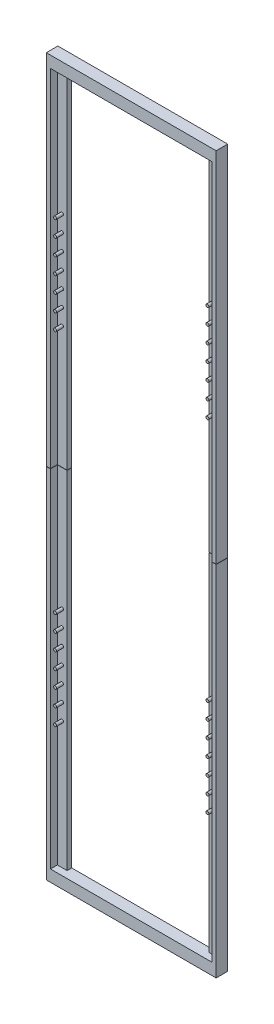
SolidWorks part; units mm, degrees
ref_plane "Front Plane" through (0, 0, 0) normal (1, 0, 0) x (0, 1, 0)
ref_plane "Top Plane" through (0, 0, 0) normal (0, 0, 1) x (0, 1, 0)
ref_plane "Right Plane" through (0, 0, 0) normal (0, 1, 0) x (-1, 0, 0)
sketch "Sketch1" plane through (0, 0, 0) normal (0, 0, 1) x (0, 1, 0)
  line L1 (-150, -30.75) -> (150, -30.75)
  line L2 (-150, -30.75) -> (-150, 30.75)
  line L3 (-150, 30.75) -> (150, 30.75)
  line L4 (150, -30.75) -> (150, 30.75)
  line L5 (-150, -30.75) -> (150, 30.75) construction
  line L6 (-150, 30.75) -> (150, -30.75) construction
  line L7 (-155, -36.75) -> (155, -36.75)
  line L8 (-155, -36.75) -> (-155, 36.75)
  line L9 (-155, 36.75) -> (155, 36.75)
  line L10 (155, -36.75) -> (155, 36.75)
  line L11 (-155, -36.75) -> (155, 36.75) construction
  line L12 (-155, 36.75) -> (155, -36.75) construction
  point P0 (0, 0)
  point P6 (0, 0)
  dimension "D1" = 61.5
  dimension "D2" = 6
  dimension "D3" = 300
  dimension "D4" = 310
extrude "Boss-Extrude1" add sketch "Sketch1" along normal blind 5
sketch "Sketch2" plane through (0, 0, 5) normal (0, 0, 1) x (1, 0, 0)
  line L1 (-30.75, 150) -> (-34.95, 150)
  line L2 (-30.75, 150) -> (-30.75, -150)
  line L3 (-30.75, -150) -> (-34.95, -150)
  line L4 (-34.95, 150) -> (-34.95, -150)
  line L5 (30.75, -150) -> (34.95, -150)
  line L6 (30.75, -150) -> (30.75, 150)
  line L7 (30.75, 150) -> (34.95, 150)
  line L8 (34.95, -150) -> (34.95, 150)
  dimension "D1" = 4.2
  dimension "D2" = 4.2
ref_plane "Plane1" through (-36.75, 155, 5) normal (0, -1, 0) x (-1, 0, 0)
extrude "Cut-Extrude1" cut sketch "Sketch2" against normal blind 3 contours L4 L3 L2 L1 | L8 L7 L6 L5
sketch "Sketch6" plane through (0, 0, 2) normal (0, 0, 1) x (1, 0, 0)
  line L4 (30.75, -150) -> (34.95, -150)
  line L5 (34.95, -150) -> (34.95, 150)
  line L6 (34.95, 150) -> (30.75, 150)
  line L7 (30.75, 150) -> (30.75, -150)
  line L8 (30.75, -150) -> (34.95, -150)
  line L9 (34.95, -150) -> (34.95, 150)
  line L10 (34.95, 150) -> (30.75, 150)
  line L11 (30.75, 150) -> (30.75, -150)
  dimension "D1" = 0
sketch "Sketch7" plane through (0, 0, 2) normal (0, 0, 1) x (1, 0, 0)
  line L0 (-31.65, 55) -> (-33.25, 55) construction
  line L1 (-34.45, 53.8) -> (-34.45, 52.2) construction
  line L2 (-33.25, 51) -> (-31.65, 51) construction
  line L3 (-30.45, 49.8) -> (-30.45, 56.2) construction
  line L4 (34.45, 66.2) -> (34.45, 67.8)
  line L5 (33.25, 69) -> (31.65, 69)
  line L6 (30.45, 70.2) -> (30.45, 63.8)
  line L7 (31.65, 65) -> (33.25, 65)
  line L8 (34.45, 66.2) -> (34.45, 67.8)
  line L9 (33.25, 69) -> (31.65, 69)
  line L10 (30.45, 70.2) -> (30.45, 63.8)
  line L11 (31.65, 65) -> (33.25, 65)
  line L12 (-31.65, 69) -> (-33.25, 69) construction
  line L13 (-34.45, 67.8) -> (-34.45, 66.2) construction
  line L14 (-33.25, 65) -> (-31.65, 65) construction
  line L15 (-30.45, 63.8) -> (-30.45, 70.2) construction
  line L16 (-31.65, -51) -> (-33.25, -51) construction
  line L17 (-34.45, -52.2) -> (-34.45, -53.8) construction
  line L18 (-33.25, -55) -> (-31.65, -55) construction
  line L19 (-30.45, -56.2) -> (-30.45, -49.8) construction
  line L20 (-31.65, -65) -> (-33.25, -65) construction
  line L21 (-34.45, -66.2) -> (-34.45, -67.8) construction
  line L22 (-33.25, -69) -> (-31.65, -69) construction
  line L23 (-30.45, -70.2) -> (-30.45, -63.8) construction
  line L24 (31.65, -69) -> (33.25, -69) construction
  line L25 (34.45, -67.8) -> (34.45, -66.2) construction
  line L26 (33.25, -65) -> (31.65, -65) construction
  line L27 (30.45, -63.8) -> (30.45, -70.2) construction
  line L28 (34.45, -53.8) -> (34.45, -52.2) construction
  line L29 (33.25, -51) -> (31.65, -51) construction
  line L30 (30.45, -49.8) -> (30.45, -56.2) construction
  line L31 (31.65, -55) -> (33.25, -55) construction
  line L32 (31.65, 51) -> (33.25, 51) construction
  line L33 (34.45, 52.2) -> (34.45, 53.8) construction
  line L34 (33.25, 55) -> (31.65, 55) construction
  line L35 (30.45, 56.2) -> (30.45, 49.8) construction
  line L36 (-31.65, 55) -> (-33.25, 55)
  line L37 (-34.45, 53.8) -> (-34.45, 52.2)
  line L38 (-33.25, 51) -> (-31.65, 51)
  line L39 (-30.45, 49.8) -> (-30.45, 56.2)
  line L40 (-31.65, 69) -> (-33.25, 69)
  line L41 (-34.45, 67.8) -> (-34.45, 66.2)
  line L42 (-33.25, 65) -> (-31.65, 65)
  line L43 (-30.45, 63.8) -> (-30.45, 70.2)
  line L44 (-31.65, -51) -> (-33.25, -51)
  line L45 (-34.45, -52.2) -> (-34.45, -53.8)
  line L46 (-33.25, -55) -> (-31.65, -55)
  line L47 (-30.45, -56.2) -> (-30.45, -49.8)
  line L48 (-31.65, -65) -> (-33.25, -65)
  line L49 (-34.45, -66.2) -> (-34.45, -67.8)
  line L50 (-33.25, -69) -> (-31.65, -69)
  line L51 (-30.45, -70.2) -> (-30.45, -63.8)
  line L52 (31.65, -69) -> (33.25, -69)
  line L53 (34.45, -67.8) -> (34.45, -66.2)
  line L54 (33.25, -65) -> (31.65, -65)
  line L55 (30.45, -63.8) -> (30.45, -70.2)
  line L56 (34.45, -53.8) -> (34.45, -52.2)
  line L57 (33.25, -51) -> (31.65, -51)
  line L58 (30.45, -49.8) -> (30.45, -56.2)
  line L59 (31.65, -55) -> (33.25, -55)
  line L60 (31.65, 51) -> (33.25, 51)
  line L61 (34.45, 52.2) -> (34.45, 53.8)
  line L62 (33.25, 55) -> (31.65, 55)
  line L63 (30.45, 56.2) -> (30.45, 49.8)
  arc A0 (-33.25, 55) -> (-34.45, 53.8) centre (-33.25, 53.8) ccw construction
  circle A1 centre (32.95, 67) radius 0.75
  circle A2 centre (32.95, 67) radius 0.75
  arc A3 (-34.45, 52.2) -> (-33.25, 51) centre (-33.25, 52.2) ccw construction
  arc A4 (-30.45, 49.8) -> (-31.65, 51) centre (-31.65, 49.8) ccw construction
  arc A5 (-31.65, 55) -> (-30.45, 56.2) centre (-31.65, 56.2) ccw construction
  arc A6 (34.45, 67.8) -> (33.25, 69) centre (33.25, 67.8) ccw
  arc A7 (30.45, 70.2) -> (31.65, 69) centre (31.65, 70.2) ccw
  arc A8 (31.65, 65) -> (30.45, 63.8) centre (31.65, 63.8) ccw
  arc A9 (33.25, 65) -> (34.45, 66.2) centre (33.25, 66.2) ccw
  arc A10 (34.45, 67.8) -> (33.25, 69) centre (33.25, 67.8) ccw
  arc A11 (30.45, 70.2) -> (31.65, 69) centre (31.65, 70.2) ccw
  arc A12 (31.65, 65) -> (30.45, 63.8) centre (31.65, 63.8) ccw
  arc A13 (33.25, 65) -> (34.45, 66.2) centre (33.25, 66.2) ccw
  arc A14 (-33.25, 69) -> (-34.45, 67.8) centre (-33.25, 67.8) ccw construction
  arc A15 (-34.45, 66.2) -> (-33.25, 65) centre (-33.25, 66.2) ccw construction
  arc A16 (-30.45, 63.8) -> (-31.65, 65) centre (-31.65, 63.8) ccw construction
  arc A17 (-31.65, 69) -> (-30.45, 70.2) centre (-31.65, 70.2) ccw construction
  arc A18 (-33.25, -51) -> (-34.45, -52.2) centre (-33.25, -52.2) ccw construction
  arc A19 (-34.45, -53.8) -> (-33.25, -55) centre (-33.25, -53.8) ccw construction
  arc A20 (-30.45, -56.2) -> (-31.65, -55) centre (-31.65, -56.2) ccw construction
  arc A21 (-31.65, -51) -> (-30.45, -49.8) centre (-31.65, -49.8) ccw construction
  arc A22 (-33.25, -65) -> (-34.45, -66.2) centre (-33.25, -66.2) ccw construction
  arc A23 (-34.45, -67.8) -> (-33.25, -69) centre (-33.25, -67.8) ccw construction
  arc A24 (-30.45, -70.2) -> (-31.65, -69) centre (-31.65, -70.2) ccw construction
  arc A25 (-31.65, -65) -> (-30.45, -63.8) centre (-31.65, -63.8) ccw construction
  arc A26 (33.25, -69) -> (34.45, -67.8) centre (33.25, -67.8) ccw construction
  arc A27 (34.45, -66.2) -> (33.25, -65) centre (33.25, -66.2) ccw construction
  arc A28 (30.45, -63.8) -> (31.65, -65) centre (31.65, -63.8) ccw construction
  arc A29 (31.65, -69) -> (30.45, -70.2) centre (31.65, -70.2) ccw construction
  arc A30 (34.45, -52.2) -> (33.25, -51) centre (33.25, -52.2) ccw construction
  arc A31 (30.45, -49.8) -> (31.65, -51) centre (31.65, -49.8) ccw construction
  arc A32 (31.65, -55) -> (30.45, -56.2) centre (31.65, -56.2) ccw construction
  arc A33 (33.25, -55) -> (34.45, -53.8) centre (33.25, -53.8) ccw construction
  arc A34 (33.25, 51) -> (34.45, 52.2) centre (33.25, 52.2) ccw construction
  arc A35 (34.45, 53.8) -> (33.25, 55) centre (33.25, 53.8) ccw construction
  arc A36 (30.45, 56.2) -> (31.65, 55) centre (31.65, 56.2) ccw construction
  arc A37 (31.65, 51) -> (30.45, 49.8) centre (31.65, 49.8) ccw construction
  arc A38 (-33.25, 55) -> (-34.45, 53.8) centre (-33.25, 53.8) ccw
  arc A39 (-34.45, 52.2) -> (-33.25, 51) centre (-33.25, 52.2) ccw
  arc A40 (-30.45, 49.8) -> (-31.65, 51) centre (-31.65, 49.8) ccw
  arc A41 (-31.65, 55) -> (-30.45, 56.2) centre (-31.65, 56.2) ccw
  arc A42 (-33.25, 69) -> (-34.45, 67.8) centre (-33.25, 67.8) ccw
  arc A43 (-34.45, 66.2) -> (-33.25, 65) centre (-33.25, 66.2) ccw
  arc A44 (-30.45, 63.8) -> (-31.65, 65) centre (-31.65, 63.8) ccw
  arc A45 (-31.65, 69) -> (-30.45, 70.2) centre (-31.65, 70.2) ccw
  arc A46 (-33.25, -51) -> (-34.45, -52.2) centre (-33.25, -52.2) ccw
  arc A47 (-34.45, -53.8) -> (-33.25, -55) centre (-33.25, -53.8) ccw
  arc A48 (-30.45, -56.2) -> (-31.65, -55) centre (-31.65, -56.2) ccw
  arc A49 (-31.65, -51) -> (-30.45, -49.8) centre (-31.65, -49.8) ccw
  arc A50 (-33.25, -65) -> (-34.45, -66.2) centre (-33.25, -66.2) ccw
  arc A51 (-34.45, -67.8) -> (-33.25, -69) centre (-33.25, -67.8) ccw
  arc A52 (-30.45, -70.2) -> (-31.65, -69) centre (-31.65, -70.2) ccw
  arc A53 (-31.65, -65) -> (-30.45, -63.8) centre (-31.65, -63.8) ccw
  arc A54 (33.25, -69) -> (34.45, -67.8) centre (33.25, -67.8) ccw
  arc A55 (34.45, -66.2) -> (33.25, -65) centre (33.25, -66.2) ccw
  arc A56 (30.45, -63.8) -> (31.65, -65) centre (31.65, -63.8) ccw
  arc A57 (31.65, -69) -> (30.45, -70.2) centre (31.65, -70.2) ccw
  arc A58 (34.45, -52.2) -> (33.25, -51) centre (33.25, -52.2) ccw
  arc A59 (30.45, -49.8) -> (31.65, -51) centre (31.65, -49.8) ccw
  arc A60 (31.65, -55) -> (30.45, -56.2) centre (31.65, -56.2) ccw
  arc A61 (33.25, -55) -> (34.45, -53.8) centre (33.25, -53.8) ccw
  arc A62 (33.25, 51) -> (34.45, 52.2) centre (33.25, 52.2) ccw
  arc A63 (34.45, 53.8) -> (33.25, 55) centre (33.25, 53.8) ccw
  arc A64 (30.45, 56.2) -> (31.65, 55) centre (31.65, 56.2) ccw
  arc A65 (31.65, 51) -> (30.45, 49.8) centre (31.65, 49.8) ccw
  circle A66 centre (32.95, 53) radius 0.75 construction
  circle A67 centre (32.95, -53) radius 0.75 construction
  circle A68 centre (32.95, -67) radius 0.75 construction
  circle A69 centre (-32.95, -67) radius 0.75 construction
  circle A70 centre (-32.95, -53) radius 0.75 construction
  circle A71 centre (-32.95, 53) radius 0.75 construction
  circle A72 centre (-32.95, 67) radius 0.75 construction
  circle A73 centre (32.95, 53) radius 0.75
  circle A74 centre (32.95, -53) radius 0.75
  circle A75 centre (32.95, -67) radius 0.75
  circle A76 centre (-32.95, -67) radius 0.75
  circle A77 centre (-32.95, -53) radius 0.75
  circle A78 centre (-32.95, 53) radius 0.75
  circle A79 centre (-32.95, 67) radius 0.75
  circle A80 centre (-32.95, -67) radius 0.65
  circle A81 centre (-32.95, -53) radius 0.65
  circle A82 centre (-32.95, 53) radius 0.65
  circle A83 centre (-32.95, 67) radius 0.65
  circle A84 centre (32.95, 67) radius 0.65
  circle A85 centre (32.95, 53) radius 0.65
  circle A86 centre (32.95, -53) radius 0.65
  circle A87 centre (32.95, -67) radius 0.65
  circle A88 centre (32.95, -60) radius 0.65
  circle A89 centre (32.95, -74) radius 0.65
  circle A90 centre (32.95, -67) radius 0.65
  circle A91 centre (32.95, -81) radius 0.65
  circle A92 centre (32.95, -74) radius 0.65
  circle A93 centre (32.95, -88) radius 0.65
  circle A94 centre (32.95, -81) radius 0.65
  circle A95 centre (32.95, -95) radius 0.65
  circle A96 centre (-32.95, -74) radius 0.65
  circle A97 centre (-32.95, -60) radius 0.65
  circle A98 centre (-32.95, -81) radius 0.65
  circle A99 centre (-32.95, -67) radius 0.65
  circle A100 centre (-32.95, -88) radius 0.65
  circle A101 centre (-32.95, -74) radius 0.65
  circle A102 centre (-32.95, -95) radius 0.65
  circle A103 centre (-32.95, -81) radius 0.65
  circle A104 centre (-32.95, 74) radius 0.65
  circle A105 centre (-32.95, 60) radius 0.65
  circle A106 centre (-32.95, 81) radius 0.65
  circle A107 centre (-32.95, 67) radius 0.65
  circle A108 centre (-32.95, 88) radius 0.65
  circle A109 centre (-32.95, 74) radius 0.65
  circle A110 centre (-32.95, 95) radius 0.65
  circle A111 centre (-32.95, 81) radius 0.65
  circle A112 centre (32.95, 60) radius 0.65
  circle A113 centre (32.95, 74) radius 0.65
  circle A114 centre (32.95, 67) radius 0.65
  circle A115 centre (32.95, 81) radius 0.65
  circle A116 centre (32.95, 74) radius 0.65
  circle A117 centre (32.95, 88) radius 0.65
  circle A118 centre (32.95, 81) radius 0.65
  circle A119 centre (32.95, 95) radius 0.65
  dimension "D3" = 0.1
  dimension "D4" = 0.1
  dimension "D5" = 0.1
  dimension "D6" = 0.1
  dimension "D7" = 0.1
  dimension "D8" = 0.1
  dimension "D9" = 0.1
  dimension "D10" = 0.1
  dimension "D1" = 0
  dimension "D2" = 0
  dimension "D11" = 5
  dimension "D12" = 5
  dimension "D13" = 5
  dimension "D14" = 5
sketch "Sketch8" plane through (0, 0, 2) normal (0, 0, 1) x (1, 0, 0)
  line L0 (34.95, 150) -> (30.75, 150) construction
  circle A0 centre (32.95, 67) radius 0.55
  circle A1 centre (32.95, 53) radius 0.55
  circle A2 centre (32.95, 53) radius 0.75 construction
  circle A3 centre (32.95, 67) radius 0.75 construction
  circle A6 centre (32.95, 60) radius 0.55
  circle A7 centre (32.95, 74) radius 0.55
  circle A8 centre (32.95, 67) radius 0.55
  circle A9 centre (32.95, 81) radius 0.55
  circle A10 centre (32.95, 74) radius 0.55
  circle A11 centre (32.95, 88) radius 0.55
  circle A12 centre (32.95, 81) radius 0.55
  circle A13 centre (32.95, 95) radius 0.55
  point P13 (32.95, 96.8)
  dimension "D1" = 0.2
  dimension "D2" = 0.2
  dimension "D3" = 53.2
  dimension "D4" = 5
extrude "Boss-Extrude2" add sketch "Sketch7" along normal blind 3 contours A82 | A83 | A84 | A85 | A86 | A87 | A81 | A88 | A89 | A91 | A93 | A80 | A95 | A97 | A96 | A98 | A100 | A105 | A104 | A106 | A108 | A102 | A110 | A119 | A117 | A115 | A113 | A112
sketch "Sketch9" plane through (0, 0, 5) normal (0, 0, 1) x (1, 0, 0)
  line L0 (-36.75, 155) -> (-36.75, -155) construction
  line L1 (36.75, 0.05) -> (-36.75, 0.05)
  line L2 (36.75, 0.05) -> (36.75, -0.05)
  line L3 (36.75, -0.05) -> (-36.75, -0.05)
  line L4 (-36.75, 0.05) -> (-36.75, -0.05)
  line L5 (36.75, 0.05) -> (-36.75, -0.05) construction
  line L6 (36.75, -0.05) -> (-36.75, 0.05) construction
  point P0 (0, 0)
  point P8 (0, 0)
  dimension "D1" = 0.1
extrude "Cut-Extrude2" cut sketch "Sketch9" against normal through all contours L3 L4 L1 L2
